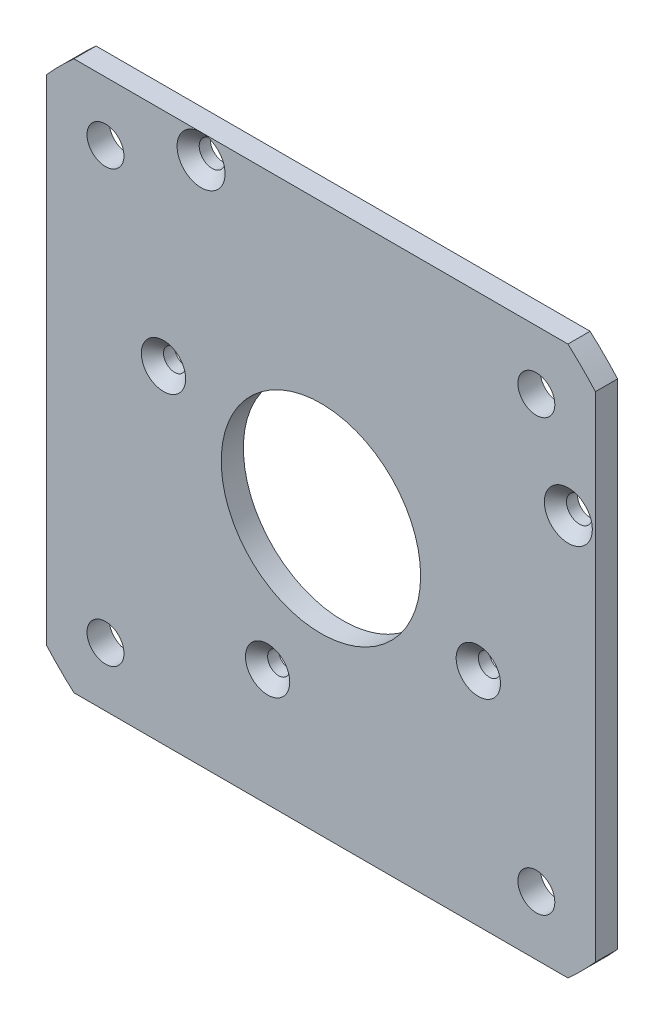
SolidWorks part; units mm, degrees
material "AISI 1020"
ref_plane "Спереди" through (0, 0, 0) normal (0, 0, 1) x (1, 0, 0)
ref_plane "Сверху" through (0, 0, 0) normal (0, 1, 0) x (1, 0, 0)
ref_plane "Справа" through (0, 0, 0) normal (1, 0, 0) x (0, 0, -1)
sketch "Эскиз1" plane through (0, 0, 0) normal (0, 0, 1) x (1, 0, 0)
  line L4 (74.3363, -66.8888) -> (74.3363, 66.8888) construction
  line L5 (-66.8888, -74.3363) -> (66.8888, -74.3363) construction
  line L6 (-74.3363, 66.8888) -> (-74.3363, -66.8888) construction
  line L7 (66.8888, 74.3363) -> (-66.8888, 74.3363) construction
  line L8 (74.3363, -66.8888) -> (74.3363, 66.8888)
  line L9 (-66.8888, -74.3363) -> (66.8888, -74.3363)
  line L10 (-74.3363, 66.8888) -> (-74.3363, -66.8888)
  line L11 (66.8888, 74.3363) -> (-66.8888, 74.3363)
  arc A3 (66.8888, -74.3363) -> (74.3363, -66.8888) centre (0, 0) ccw construction
  arc A4 (74.3363, 66.8888) -> (66.8888, 74.3363) centre (0, 0) ccw construction
  arc A5 (-74.3363, -66.8888) -> (-66.8888, -74.3363) centre (0, 0) ccw construction
  arc A6 (-66.8888, 74.3363) -> (-74.3363, 66.8888) centre (0, 0) ccw construction
  arc A7 (66.8888, -74.3363) -> (74.3363, -66.8888) centre (0, 0) ccw
  arc A8 (74.3363, 66.8888) -> (66.8888, 74.3363) centre (0, 0) ccw
  arc A9 (-74.3363, -66.8888) -> (-66.8888, -74.3363) centre (0, 0) ccw
  arc A10 (-66.8888, 74.3363) -> (-74.3363, 66.8888) centre (0, 0) ccw
  circle A11 centre (-58.3363, -58.3363) radius 5 construction
  circle A12 centre (-58.3363, 58.3363) radius 5 construction
  circle A13 centre (58.3363, 58.3363) radius 5 construction
  circle A14 centre (58.3363, -58.3363) radius 5 construction
  circle A15 centre (-58.3363, -58.3363) radius 5
  circle A16 centre (-58.3363, 58.3363) radius 5
  circle A17 centre (58.3363, 58.3363) radius 5
  circle A18 centre (58.3363, -58.3363) radius 5
  circle A21 centre (0, 0) radius 27
  circle A22 centre (0, 0) radius 27
  dimension "D1" = 2
base flange "Базовая кромка1" sketch "Эскиз1" thickness 6 reverse thickness direction no parameters "D1"=0.75
sketch "Эскиз6" plane through (0, 0, 0) normal (0, 0, 1) x (1, 0, 0)
  circle A0 centre (-32.4545, 67.8363) radius 3.5 construction
  circle A1 centre (-42.6219, 14.4351) radius 3 construction
  circle A2 centre (-14.4351, -42.6219) radius 3 construction
  circle A3 centre (42.6219, -14.4351) radius 3 construction
  circle A4 centre (66.9966, 34.1543) radius 3.5 construction
  circle A5 centre (-32.4545, 67.8363) radius 3.5
  circle A6 centre (-42.6219, 14.4351) radius 3
  circle A7 centre (-14.4351, -42.6219) radius 3
  circle A8 centre (42.6219, -14.4351) radius 3
  circle A9 centre (66.9966, 34.1543) radius 3.5
extrude "Вырез-Вытянуть1" cut sketch "Эскиз6" against normal through all
chamfer "Фаска1" distance 3 angle 45 5 edges at (-28.9545, 67.8363, 0) (-39.6219, 14.4351, 0) (-11.4351, -42.6219, 0) (45.6219, -14.4351, 0) (70.4966, 34.1543, 0)
chamfer "Фаска2" [suppressed] distance 3 angle 45
sketch "Сгиб-Линии1" [suppressed] plane through (0, 0, 0) normal (0, 1, 0) x (1, 0, 0)
sketch "Граничная рамка1" [suppressed] plane through (0, 0, 0) normal (0, 1, 0) x (1, 0, 0)
sheet metal parameters "Листовой металл3" thickness 6 parameters "D1"=0.75
flat pattern "Развертка3" [suppressed]
sketch "Сгиб-Линии2" plane through (0, 0, 0) normal (0, 1, 0) x (1, 0, 0)
sketch "Граничная рамка2" [suppressed] plane through (0, 0, 0) normal (0, 1, 0) x (1, 0, 0)
sheet metal parameters "Листовой металл4" thickness 6 parameters "D1"=0.75
flat pattern "Развертка3"
sketch "Сгиб-Линии2" plane through (0, 0, 0) normal (0, 1, 0) x (1, 0, 0)
sketch3d "Граничная рамка2" [suppressed]
  line L0 (74.3363, 74.3363, -6) -> (74.3363, -74.3363, -6) construction
  line L1 (-74.3363, 74.3363, -6) -> (-74.3363, -74.3363, -6) construction
  line L2 (74.3363, 74.3363, -6) -> (-74.3363, 74.3363, -6) construction
  line L3 (74.3363, -74.3363, -6) -> (-74.3363, -74.3363, -6) construction
